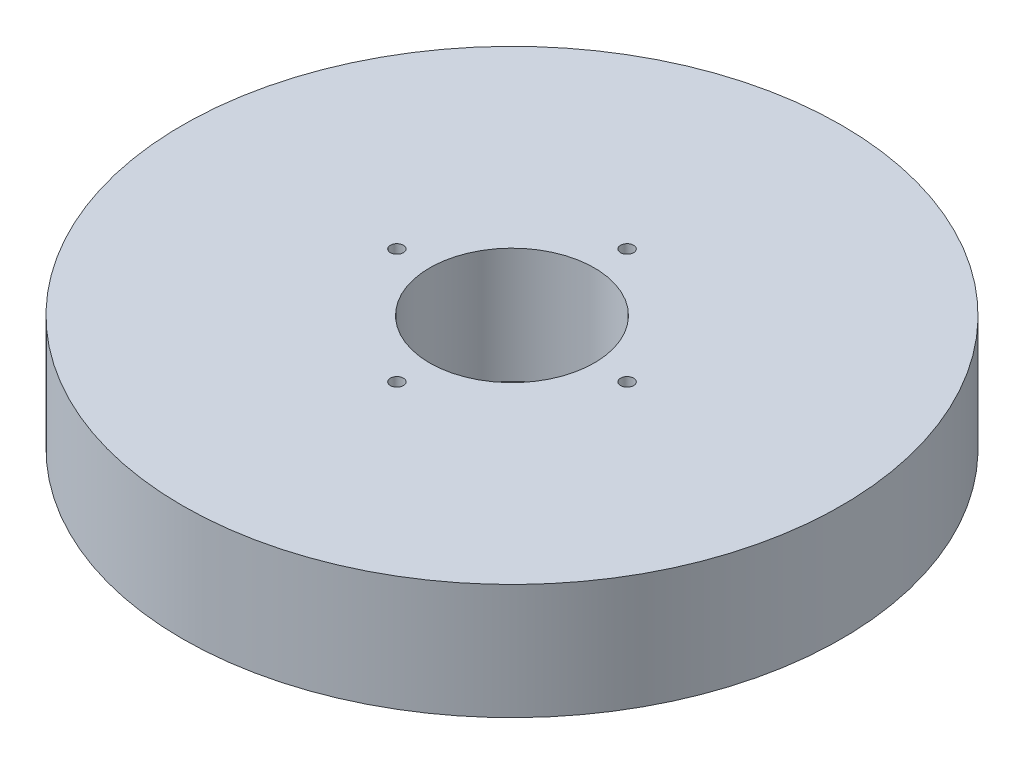
SolidWorks part; units mm, degrees
ref_plane "Front Plane" through (0, 0, 0) normal (0, 0, 1) x (1, 0, 0)
ref_plane "Top Plane" through (0, 0, 0) normal (0, 1, 0) x (1, 0, 0)
ref_plane "Right Plane" through (0, 0, 0) normal (1, 0, 0) x (0, 0, -1)
sketch "Sketch1" plane through (0, 0, 0) normal (0, 1, 0) x (1, 0, 0)
  circle A0 centre (0, 0) radius 80
  dimension "FLANGE_OD" = 160
extrude "Boss-Extrude1" add sketch "Sketch1" along normal blind 28
sketch "Sketch2" plane through (0, 0, 0) normal (0, 1, 0) x (1, 0, 0)
  circle A0 centre (0, 0) radius 20
  dimension "BORE_D" = 40
extrude "Cut-Extrude1" cut sketch "Sketch2" along normal through all
sketch "Sketch3" plane through (0, 28, 0) normal (0, 1, 0) x (1, 0, 0)
  circle A0 centre (0, 0) radius 27.942 construction
  circle A1 centre (-27.942, 0) radius 1.5778
  dimension "BOLT_D" = 3.1556
  dimension "BOLT_PCD" = 55.884
extrude "Cut-Extrude2" cut sketch "Sketch3" against normal blind 22.3686
pattern_circular "CirPattern1" count 4 over 360 about axis through (0, 0, 0) along (0, 1, 0) of "Cut-Extrude2"
